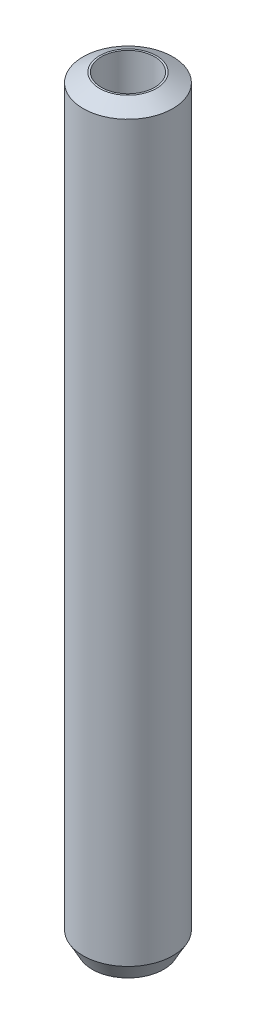
SolidWorks part; units mm, degrees
ref_plane "Front Plane" through (0, 0, 0) normal (0, 0, 1) x (1, 0, 0)
ref_plane "Top Plane" through (0, 0, 0) normal (0, 1, 0) x (1, 0, 0)
ref_plane "Right Plane" through (0, 0, 0) normal (1, 0, 0) x (0, 0, -1)
sketch "Sketch1" plane through (0, 0, 0) normal (0, 1, 0) x (1, 0, 0)
  circle A0 centre (0, 0) radius 25
  dimension "SHAFT_OD" = 50
extrude "Boss-Extrude1" add sketch "Sketch1" along normal blind 422.8885
sketch "Sketch2" plane through (0, 0, 0) normal (0, 1, 0) x (1, 0, 0)
  circle A0 centre (0, 0) radius 14.8226
  dimension "BORE_D" = 29.6452
extrude "Cut-Extrude1" cut sketch "Sketch2" along normal through all
chamfer "Chamfer1" distance 5.1019 angle 60.921 2 edges at (0, 422.8885, 25) (0, 0, 25) first distance on face at (0, 422.8885, 25) first distance on face at (0, 0, 14.8226)
